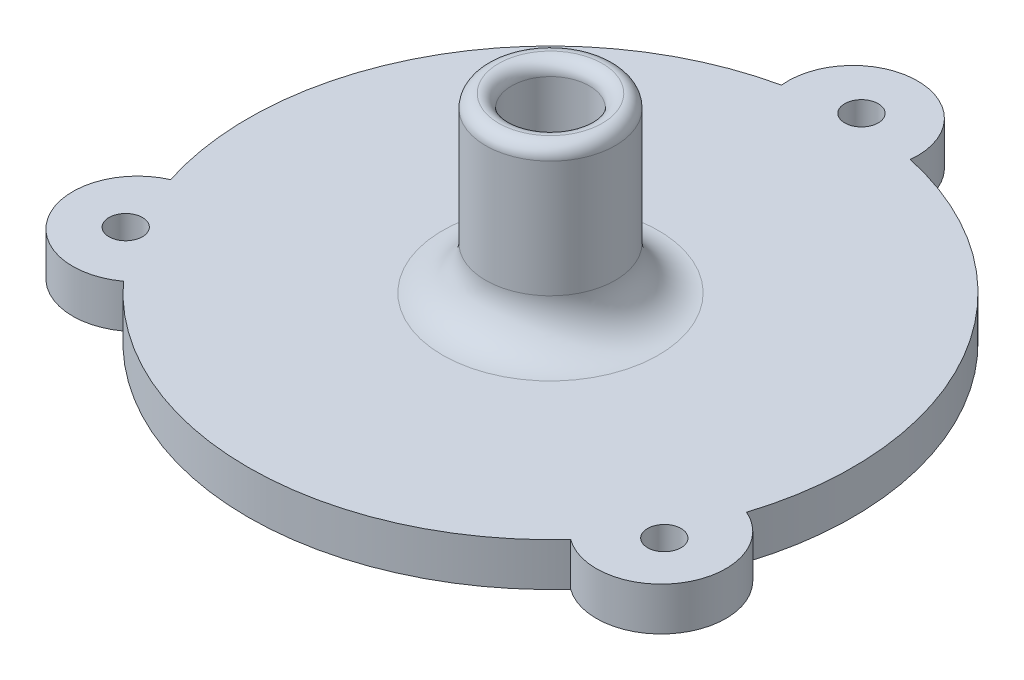
SolidWorks part; units mm, degrees
ref_plane "Front Plane" through (0, 0, 0) normal (0, 0, 1) x (1, 0, 0)
ref_plane "Top Plane" through (0, 0, 0) normal (0, 1, 0) x (1, 0, 0)
ref_plane "Right Plane" through (0, 0, 0) normal (1, 0, 0) x (0, 0, -1)
sketch "Sketch1" plane through (0, 0, 0) normal (0, 1, 0) x (1, 0, 0)
  circle A0 centre (0, 0) radius 28
  dimension "D1" = 56
extrude "Boss-Extrude1" add sketch "Sketch1" along normal blind 4
sketch "Sketch2" plane through (0, 4, 0) normal (0, 1, 0) x (1, 0, 0)
  circle A0 centre (0, 28) radius 6
  circle A1 centre (0, 0) radius 28 construction
  circle A2 centre (24.2487, -14) radius 6
  circle A3 centre (-24.2487, -14) radius 6
  point P10 (0, 0)
  dimension "D1" = 12
  dimension "D2" = 3
extrude "Boss-Extrude2" add sketch "Sketch2" against normal blind 4
sketch "Sketch3" plane through (0, 4, 0) normal (0, 1, 0) x (1, 0, 0)
  circle A0 centre (0, 28.8) radius 1.55
  arc A1 (5.9655, 27.3571) -> (-5.9655, 27.3571) centre (0, 28) ccw construction
  circle A2 centre (24.9415, -14.4) radius 1.55
  circle A3 centre (-24.9415, -14.4) radius 1.55
  point P12 (0, 0)
  dimension "D1" = 3.1
  dimension "D2" = 0.8
  dimension "D3" = 3
extrude "Cut-Extrude1" cut sketch "Sketch3" against normal through all
sketch "Sketch4" plane through (0, 4, 0) normal (0, 1, 0) x (1, 0, 0)
  circle A0 centre (0, 0) radius 3.6
  dimension "D1" = 7.2
extrude "Cut-Extrude2" cut sketch "Sketch4" against normal through all
sketch "Sketch5" plane through (0, 4, 0) normal (0, 1, 0) x (1, 0, 0)
  circle A0 centre (0, 0) radius 3.6
  circle A1 centre (0, 0) radius 6
  dimension "D1" = 2.4
extrude "Boss-Extrude3" add sketch "Sketch5" along normal blind 16
fillet "Fillet1" radius 4 1 edges at (0, 4, 6)
fillet "Fillet2" radius 1.2 2 edges at (0, 20, 3.6) (0, 20, 6)
fillet "Fillet3" radius 2 1 edges at (0, 0, 3.6)
equation "\"D1@Sketch4\"=12-4.8"
